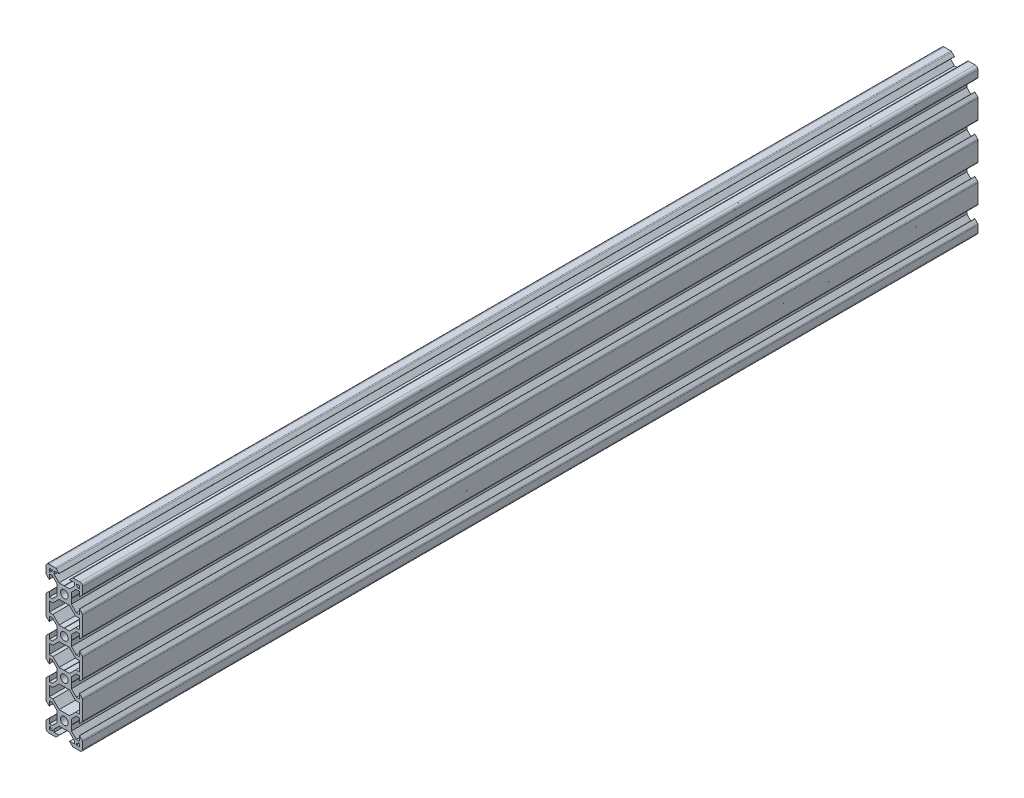
SolidWorks part; units mm, degrees
material "6063-T5"
ref_plane "Front Plane" through (0, 0, 0) normal (0, 0, 1) x (1, 0, 0)
ref_plane "Top Plane" through (0, 0, 0) normal (0, 1, 0) x (1, 0, 0)
ref_plane "Right Plane" through (0, 0, 0) normal (1, 0, 0) x (0, 0, -1)
sketch "Sketch2" plane through (0, 0, 0) normal (0, 0, 1) x (1, 0, 0)
  line L0 (-8.2, 2.8875) -> (-8.2, 5.4975)
  line L3 (-4.9072, 9.9975) -> (-8.5, 9.9975)
  line L4 (-10, 4.9047) -> (-10, 8.4975)
  line L5 (-2.1, 0) -> (-3.8, 0) construction
  line L6 (0, 3.8) -> (0, 2.1) construction
  line L7 (-0.1, 3.9) -> (-2.8404, 3.9)
  line L8 (-3.9, 0.1) -> (-3.9, 2.8383)
  line L9 (-2.89, 8.1975) -> (-5.5, 8.1975)
  line L10 (-6.57, 8.1975) -> (-6.57, 7.6575)
  line L11 (-8.2, 6.5675) -> (-7.66, 6.5675)
  line L12 (-5.5, 8.1975) -> (-5.5, 6.5588)
  line L13 (-6.56, 5.4975) -> (-8.2, 5.4975)
  line L14 (-8.2, 8.1975) -> (-1.4852, 1.4847) construction
  line L15 (-6.56, 5.4975) -> (-3.9, 2.8383)
  line L16 (-5.5, 6.5588) -> (-2.8404, 3.9)
  line L17 (-7.66, 6.5675) -> (-6.57, 7.6575)
  line L18 (-8.7302, 7.6671) -> (-0.5302, -0.5304) construction
  line L19 (-7.6698, 8.7279) -> (0.5302, 0.5304) construction
  line L20 (-8.2, 8.1975) -> (0, 0) construction
  line L21 (-8.2, 6.5675) -> (-8.2, 8.1975)
  line L22 (-8.2, -0.0025) -> (-8.2, 8.1975) construction
  line L23 (-6.57, 8.1975) -> (-8.2, 8.1975)
  line L24 (0, 8.1975) -> (-8.2, 8.1975) construction
  line L25 (-10, -0.0025) -> (-10, 9.9975) construction
  line L26 (0, 9.9975) -> (-10, 9.9975) construction
  line L27 (-2.89, 8.3075) -> (-2.89, 8.1975)
  line L29 (-8.31, 2.8875) -> (-8.2, 2.8875)
  line L30 (-4.3486, 9.7661) -> (-2.89, 8.3075)
  line L31 (-8.31, 2.8875) -> (-9.7686, 4.3461)
  line L34 (-0.1, 3.9) -> (0, 3.8)
  line L35 (-3.9, 0.1) -> (-3.8, 0)
  line L36 (-10, -20) -> (0, -20) construction
  line L37 (0, 0) -> (0, -20) construction
  line L38 (0, -3.9) -> (-2.8404, -3.9)
  line L39 (-3.8, 0) -> (-3.9, -0.1)
  line L40 (-3.9, -0.1) -> (-3.9, -2.84)
  line L41 (-2.8404, -3.9) -> (-6.25, -7.3096)
  line L42 (-3.9, -2.84) -> (-6.56, -5.5)
  line L43 (-8.21, -2.89) -> (-8.21, -5.5)
  line L44 (-6.56, 5.4975) -> (-6.56, -5.5) construction
  line L45 (-6.56, -5.5) -> (-8.21, -5.5)
  line L46 (-6.25, -7.3096) -> (-6.25, -12.7) construction
  line L47 (-6.25, -7.3096) -> (-8.21, -7.3096)
  line L48 (-8.21, -2.89) -> (-8.31, -2.89)
  line L49 (-8.31, -2.89) -> (-9.7657, -4.3457)
  line L51 (-8.21, -7.3096) -> (-8.21, -12.7)
  line L52 (-0.1, -16.1) -> (-2.85, -16.1)
  line L53 (-3.9, -17.16) -> (-3.9, -19.9)
  line L54 (-6.25, -12.7) -> (-2.85, -16.1)
  line L58 (-3.9, -17.16) -> (-6.56, -14.5)
  line L60 (-8.21, -17.11) -> (-8.31, -17.11)
  line L61 (-10, -4.9114) -> (-10, -15.0886)
  line L62 (-9.7657, -15.6543) -> (-8.31, -17.11)
  line L63 (-0.1, -16.1) -> (0, -16.2)
  line L64 (-3.9, -19.9) -> (-3.8, -20)
  line L65 (-8.21, -14.5) -> (-6.56, -14.5)
  line L66 (-8.21, -12.7) -> (-6.25, -12.7)
  line L67 (-10, -30.01) -> (0, -30.01) construction
  line L68 (-8.21, -14.5) -> (-8.21, -17.11)
  line L69 (-3.9, -20.1) -> (-3.8, -20)
  line L71 (-10, -20) -> (0, -20) construction
  line L72 (-8.21, -30.01) -> (-8.21, -27.31)
  line L73 (-10, -30.01) -> (-10, -24.9101)
  line L74 (-8.21, -25.4987) -> (-8.21, -22.8887)
  line L76 (-8.21, -27.31) -> (-6.25, -27.31)
  line L77 (-8.21, -25.4987) -> (-6.56, -25.4987)
  line L85 (-0.1, -23.9) -> (0, -23.8)
  line L95 (-9.7657, -24.3444) -> (-8.31, -22.8887)
  line L96 (-8.21, -22.8887) -> (-8.31, -22.8887)
  line L97 (-3.9, -22.8387) -> (-6.56, -25.4987)
  line L98 (-6.25, -27.31) -> (-2.84, -23.9)
  line L99 (-3.9, -22.8387) -> (-3.9, -20.1)
  line L100 (-0.1, -23.9) -> (-2.84, -23.9)
  arc A1 (-10, 8.4975) -> (-8.5, 9.9975) centre (-8.5, 8.4975) cw
  arc A2 (-9.7686, 4.3461) -> (-10, 4.9047) centre (-9.21, 4.9047) cw
  arc A3 (-4.3486, 9.7661) -> (-4.9072, 9.9975) centre (-4.9072, 9.2075) ccw
  arc A5 (0, 2.1) -> (0, -2.1) centre (0, 0) ccw
  arc A6 (-9.7657, -15.6543) -> (-10, -15.0886) centre (-9.2, -15.0886) cw
  arc A7 (-9.7657, -4.3457) -> (-10, -4.9114) centre (-9.2, -4.9114) ccw
  arc A8 (0, -17.9) -> (0, -22.1) centre (0, -20) ccw
  arc A10 (-9.7657, -24.3444) -> (-10, -24.9101) centre (-9.2, -24.9101) ccw
  point P29 (-10, 9.9975)
  point P39 (-10, 4.5775)
  point P42 (-4.58, 9.9975)
  point P76 (-10, -15.42)
  point P79 (-10, -4.58)
  dimension "D15" = 1.5
  dimension "D22" = 0.79
  dimension "D30" = 2.1
  dimension "D31" = 2.1
  dimension "D51" = 0.8
  dimension "D52" = 2.61
  dimension "D64" = 1.65
  dimension "D53" = 0.8
  dimension "D55" = 3.9
  dimension "D4" = 1.8
  dimension "D5" = 3.43
  dimension "D6" = 3.43
  dimension "D7" = 0.54
  dimension "D8" = 0.54
  dimension "D9" = 1.07
  dimension "D10" = 1.07
  dimension "D11" = 3.9
  dimension "D12" = 3.9
  dimension "D16" = 7.11
  dimension "D17" = 0.11
  dimension "D18" = 1.69
  dimension "D19" = 0.11
  dimension "D20" = 7.11
  dimension "D21" = 1.69
  dimension "D23" = 10
  dimension "D24" = 0.1
  dimension "D25" = 45
  dimension "D26" = 0.1
  dimension "D27" = 45
  dimension "D28" = 1.64
  dimension "D29" = 20
  dimension "D32" = 3.9
  dimension "D33" = 45
  dimension "D34" = 2.74
  dimension "D35" = 45
  dimension "D36" = 1.96
  dimension "D37" = 2.61
  dimension "D38" = 90
  dimension "D39" = 2.61
  dimension "D40" = 3.9
  dimension "D41" = 3.9
  dimension "D42" = 135
  dimension "D44" = 45
  dimension "D45" = 1.8
  dimension "D46" = 0.1
  dimension "D47" = 0.1
  dimension "D48" = 45
  dimension "D49" = 0.1
  dimension "D50" = 45
  dimension "D43" = 5.5
  dimension "D54" = 3.9
  dimension "D56" = 45
  dimension "D57" = 2.7
  dimension "D59" = 45
  dimension "D60" = 0.1
  dimension "D61" = 0.1
  dimension "D62" = 45
  dimension "D63" = 2.84
  dimension "D65" = 1.96
  dimension "D66" = 45
  dimension "D67" = 1.5
  dimension "D13" = 0.75
  dimension "D14" = 0.75
sketch "Sketch3" plane through (0, 0, 0) normal (0, 0, 1) x (1, 0, 0)
  line L0 (-0.1, 3.9) -> (0, 3.8) construction
  line L1 (-0.1, 3.9) -> (-2.8404, 3.9) construction
  line L2 (-5.5, 6.5588) -> (-2.8404, 3.9) construction
  line L3 (-5.5, 8.1975) -> (-5.5, 6.5588) construction
  line L4 (-2.89, 8.1975) -> (-5.5, 8.1975) construction
  line L5 (-7.66, 6.5675) -> (-6.57, 7.6575)
  line L6 (-6.57, 7.6575) -> (-6.57, 8.1975)
  line L7 (-6.57, 8.1975) -> (-8.2, 8.1975)
  line L8 (-8.2, 8.1975) -> (-8.2, 6.5675)
  line L9 (-8.2, 6.5675) -> (-7.66, 6.5675)
  line L10 (-7.66, 6.5675) -> (-6.57, 7.6575)
  line L11 (-6.57, 7.6575) -> (-6.57, 8.1975)
  line L12 (-6.57, 8.1975) -> (-8.2, 8.1975)
  line L13 (-8.2, 8.1975) -> (-8.2, 6.5675)
  line L14 (-8.2, 6.5675) -> (-7.66, 6.5675)
  line L15 (-2.89, 8.3075) -> (-2.89, 8.1975) construction
  line L16 (-4.3486, 9.7661) -> (-2.89, 8.3075) construction
  line L17 (-4.9072, 9.9975) -> (-8.5, 9.9975) construction
  line L18 (-10, 4.9047) -> (-10, 8.4975) construction
  line L19 (-8.31, 2.8875) -> (-9.7686, 4.3461) construction
  line L20 (-8.31, 2.8875) -> (-8.2, 2.8875) construction
  line L21 (-8.2, 2.8875) -> (-8.2, 5.4975) construction
  line L22 (-6.56, 5.4975) -> (-8.2, 5.4975) construction
  line L23 (-6.56, 5.4975) -> (-3.9, 2.8383) construction
  line L24 (-3.9, 0.1) -> (-3.9, 2.8383) construction
  line L25 (-3.9, 0.1) -> (-3.8, 0) construction
  line L26 (-3.8, 0) -> (-3.9, -0.1) construction
  line L27 (-3.9, -0.1) -> (-3.9, -2.84) construction
  line L28 (-3.9, -2.84) -> (-6.56, -5.5) construction
  line L29 (-6.56, -5.5) -> (-8.21, -5.5) construction
  line L30 (-8.21, -2.89) -> (-8.21, -5.5) construction
  line L31 (-8.21, -2.89) -> (-8.31, -2.89) construction
  line L32 (-8.31, -2.89) -> (-9.7657, -4.3457) construction
  line L33 (-10, -4.9114) -> (-10, -15.0886) construction
  line L34 (-9.7657, -15.6543) -> (-8.31, -17.11) construction
  line L35 (-8.21, -17.11) -> (-8.31, -17.11) construction
  line L36 (-8.21, -14.5) -> (-8.21, -17.11) construction
  line L37 (-8.21, -14.5) -> (-6.56, -14.5) construction
  line L38 (-3.9, -17.16) -> (-6.56, -14.5) construction
  line L39 (-3.9, -17.16) -> (-3.9, -19.9) construction
  line L40 (-3.9, -19.9) -> (-3.8, -20) construction
  line L41 (-3.9, -20.1) -> (-3.8, -20) construction
  line L42 (-3.9, -22.8387) -> (-3.9, -20.1) construction
  line L43 (-3.9, -22.8387) -> (-6.56, -25.4987) construction
  line L44 (-8.21, -25.4987) -> (-6.56, -25.4987) construction
  line L45 (-8.21, -25.4987) -> (-8.21, -22.8887) construction
  line L46 (-8.21, -22.8887) -> (-8.31, -22.8887) construction
  line L47 (-9.7657, -24.3444) -> (-8.31, -22.8887) construction
  line L48 (-10, -30.01) -> (-10, -24.9101) construction
  line L49 (0, -3.9) -> (-2.8404, -3.9) construction
  line L50 (-2.8404, -3.9) -> (-6.25, -7.3096) construction
  line L51 (-6.25, -7.3096) -> (-8.21, -7.3096) construction
  line L52 (-8.21, -7.3096) -> (-8.21, -12.7) construction
  line L53 (-8.21, -12.7) -> (-6.25, -12.7) construction
  line L54 (-6.25, -12.7) -> (-2.85, -16.1) construction
  line L55 (-0.1, -16.1) -> (-2.85, -16.1) construction
  line L56 (-0.1, -16.1) -> (0, -16.2) construction
  line L57 (-0.1, -23.9) -> (0, -23.8) construction
  line L58 (-0.1, -23.9) -> (-2.84, -23.9) construction
  line L59 (-6.25, -27.31) -> (-2.84, -23.9) construction
  line L60 (-8.21, -27.31) -> (-6.25, -27.31) construction
  line L61 (-8.21, -30.01) -> (-8.21, -27.31) construction
  line L62 (-0.1, 3.9) -> (0, 3.8)
  line L63 (-0.1, 3.9) -> (-2.8404, 3.9)
  line L64 (-5.5, 6.5588) -> (-2.8404, 3.9)
  line L65 (-5.5, 8.1975) -> (-5.5, 6.5588)
  line L66 (-2.89, 8.1975) -> (-5.5, 8.1975)
  line L67 (-2.89, 8.3075) -> (-2.89, 8.1975)
  line L68 (-4.3486, 9.7661) -> (-2.89, 8.3075)
  line L69 (-4.9072, 9.9975) -> (-8.5, 9.9975)
  line L70 (-10, 4.9047) -> (-10, 8.4975)
  line L71 (-8.31, 2.8875) -> (-9.7686, 4.3461)
  line L72 (-8.31, 2.8875) -> (-8.2, 2.8875)
  line L73 (-8.2, 2.8875) -> (-8.2, 5.4975)
  line L74 (-6.56, 5.4975) -> (-8.2, 5.4975)
  line L75 (-6.56, 5.4975) -> (-3.9, 2.8383)
  line L76 (-3.9, 0.1) -> (-3.9, 2.8383)
  line L77 (-3.9, 0.1) -> (-3.8, 0)
  line L78 (-3.8, 0) -> (-3.9, -0.1)
  line L79 (-3.9, -0.1) -> (-3.9, -2.84)
  line L80 (-3.9, -2.84) -> (-6.56, -5.5)
  line L81 (-6.56, -5.5) -> (-8.21, -5.5)
  line L82 (-8.21, -2.89) -> (-8.21, -5.5)
  line L83 (-8.21, -2.89) -> (-8.31, -2.89)
  line L84 (-8.31, -2.89) -> (-9.7657, -4.3457)
  line L85 (-10, -4.9114) -> (-10, -15.0886)
  line L86 (-9.7657, -15.6543) -> (-8.31, -17.11)
  line L87 (-8.21, -17.11) -> (-8.31, -17.11)
  line L88 (-8.21, -14.5) -> (-8.21, -17.11)
  line L89 (-8.21, -14.5) -> (-6.56, -14.5)
  line L90 (-3.9, -17.16) -> (-6.56, -14.5)
  line L91 (-3.9, -17.16) -> (-3.9, -19.9)
  line L92 (-3.9, -19.9) -> (-3.8, -20)
  line L93 (-3.9, -20.1) -> (-3.8, -20)
  line L94 (-3.9, -22.8387) -> (-3.9, -20.1)
  line L95 (-3.9, -22.8387) -> (-6.56, -25.4987)
  line L96 (-8.21, -25.4987) -> (-6.56, -25.4987)
  line L97 (-8.21, -25.4987) -> (-8.21, -22.8887)
  line L98 (-8.21, -22.8887) -> (-8.31, -22.8887)
  line L99 (-9.7657, -24.3444) -> (-8.31, -22.8887)
  line L100 (-10, -35.1099) -> (-10, -24.9101)
  line L101 (2.8404, -3.9) -> (-2.8404, -3.9)
  line L102 (-2.8404, -3.9) -> (-6.25, -7.3096)
  line L103 (-6.25, -7.3096) -> (-8.21, -7.3096)
  line L104 (-8.21, -7.3096) -> (-8.21, -12.7)
  line L105 (-8.21, -12.7) -> (-6.25, -12.7)
  line L106 (-6.25, -12.7) -> (-2.85, -16.1)
  line L107 (-0.1, -16.1) -> (-2.85, -16.1)
  line L108 (-0.1, -16.1) -> (0, -16.2)
  line L109 (-0.1, -23.9) -> (0, -23.8)
  line L110 (-0.1, -23.9) -> (-2.84, -23.9)
  line L111 (-6.25, -27.31) -> (-2.84, -23.9)
  line L112 (-8.21, -27.31) -> (-6.25, -27.31)
  line L113 (-8.21, -32.71) -> (-8.21, -27.31)
  line L114 (0, 0) -> (0, -20) construction
  line L115 (-10, -30.01) -> (0, -30.01) construction
  line L116 (0, 0) -> (0, -20) construction
  line L117 (-10, -30.01) -> (10, -30.01) construction
  line L118 (8.21, -32.71) -> (8.21, -27.31)
  line L119 (8.21, -27.31) -> (6.25, -27.31)
  line L120 (6.25, -27.31) -> (2.84, -23.9)
  line L121 (0.1, -23.9) -> (2.84, -23.9)
  line L122 (0.1, -23.9) -> (0, -23.8)
  line L123 (0.1, -16.1) -> (0, -16.2)
  line L124 (0.1, -16.1) -> (2.85, -16.1)
  line L125 (6.25, -12.7) -> (2.85, -16.1)
  line L126 (8.21, -12.7) -> (6.25, -12.7)
  line L127 (8.21, -7.3096) -> (8.21, -12.7)
  line L128 (6.25, -7.3096) -> (8.21, -7.3096)
  line L129 (2.8404, -3.9) -> (6.25, -7.3096)
  line L130 (10, -35.1099) -> (10, -24.9101)
  line L131 (9.7657, -24.3444) -> (8.31, -22.8887)
  line L132 (8.21, -22.8887) -> (8.31, -22.8887)
  line L133 (8.21, -25.4987) -> (8.21, -22.8887)
  line L134 (8.21, -25.4987) -> (6.56, -25.4987)
  line L135 (3.9, -22.8387) -> (6.56, -25.4987)
  line L136 (3.9, -22.8387) -> (3.9, -20.1)
  line L137 (3.9, -20.1) -> (3.8, -20)
  line L138 (3.9, -19.9) -> (3.8, -20)
  line L139 (3.9, -17.16) -> (3.9, -19.9)
  line L140 (3.9, -17.16) -> (6.56, -14.5)
  line L141 (8.21, -14.5) -> (6.56, -14.5)
  line L142 (8.21, -14.5) -> (8.21, -17.11)
  line L143 (8.21, -17.11) -> (8.31, -17.11)
  line L144 (9.7657, -15.6543) -> (8.31, -17.11)
  line L145 (10, -4.9114) -> (10, -15.0886)
  line L146 (8.31, -2.89) -> (9.7657, -4.3457)
  line L147 (8.21, -2.89) -> (8.31, -2.89)
  line L148 (8.21, -2.89) -> (8.21, -5.5)
  line L149 (6.56, -5.5) -> (8.21, -5.5)
  line L150 (3.9, -2.84) -> (6.56, -5.5)
  line L151 (3.9, -0.1) -> (3.9, -2.84)
  line L152 (3.8, 0) -> (3.9, -0.1)
  line L153 (3.9, 0.1) -> (3.8, 0)
  line L154 (3.9, 0.1) -> (3.9, 2.8383)
  line L155 (6.56, 5.4975) -> (3.9, 2.8383)
  line L156 (6.56, 5.4975) -> (8.2, 5.4975)
  line L157 (8.2, 2.8875) -> (8.2, 5.4975)
  line L158 (8.31, 2.8875) -> (8.2, 2.8875)
  line L159 (8.31, 2.8875) -> (9.7686, 4.3461)
  line L160 (10, 4.9047) -> (10, 8.4975)
  line L161 (4.9072, 9.9975) -> (8.5, 9.9975)
  line L162 (4.3486, 9.7661) -> (2.89, 8.3075)
  line L163 (2.89, 8.3075) -> (2.89, 8.1975)
  line L164 (2.89, 8.1975) -> (5.5, 8.1975)
  line L165 (5.5, 8.1975) -> (5.5, 6.5588)
  line L166 (5.5, 6.5588) -> (2.8404, 3.9)
  line L167 (0.1, 3.9) -> (2.8404, 3.9)
  line L168 (0.1, 3.9) -> (0, 3.8)
  line L169 (8.2, 6.5675) -> (7.66, 6.5675)
  line L170 (8.2, 8.1975) -> (8.2, 6.5675)
  line L171 (6.57, 8.1975) -> (8.2, 8.1975)
  line L172 (6.57, 7.6575) -> (6.57, 8.1975)
  line L173 (7.66, 6.5675) -> (6.57, 7.6575)
  line L174 (0, -60.02) -> (0, -40.02) construction
  line L175 (7.66, -66.5875) -> (6.57, -67.6775)
  line L176 (6.57, -67.6775) -> (6.57, -68.2175)
  line L177 (6.57, -68.2175) -> (8.2, -68.2175)
  line L178 (8.2, -68.2175) -> (8.2, -66.5875)
  line L179 (8.2, -66.5875) -> (7.66, -66.5875)
  line L180 (0.1, -63.92) -> (0, -63.82)
  line L181 (0.1, -63.92) -> (2.8404, -63.92)
  line L182 (5.5, -66.5788) -> (2.8404, -63.92)
  line L183 (5.5, -68.2175) -> (5.5, -66.5788)
  line L184 (2.89, -68.2175) -> (5.5, -68.2175)
  line L185 (2.89, -68.3275) -> (2.89, -68.2175)
  line L186 (4.3486, -69.7861) -> (2.89, -68.3275)
  line L187 (4.9072, -70.0175) -> (8.5, -70.0175)
  line L188 (10, -64.9247) -> (10, -68.5175)
  line L189 (8.31, -62.9075) -> (9.7686, -64.3661)
  line L190 (8.31, -62.9075) -> (8.2, -62.9075)
  line L191 (8.2, -62.9075) -> (8.2, -65.5175)
  line L192 (6.56, -65.5175) -> (8.2, -65.5175)
  line L193 (6.56, -65.5175) -> (3.9, -62.8583)
  line L194 (3.9, -60.12) -> (3.9, -62.8583)
  line L195 (3.9, -60.12) -> (3.8, -60.02)
  line L196 (3.8, -60.02) -> (3.9, -59.92)
  line L197 (3.9, -59.92) -> (3.9, -57.18)
  line L198 (3.9, -57.18) -> (6.56, -54.52)
  line L199 (6.56, -54.52) -> (8.21, -54.52)
  line L200 (8.21, -57.13) -> (8.21, -54.52)
  line L201 (8.21, -57.13) -> (8.31, -57.13)
  line L202 (8.31, -57.13) -> (9.7657, -55.6743)
  line L203 (10, -55.1086) -> (10, -44.9314)
  line L204 (9.7657, -44.3657) -> (8.31, -42.91)
  line L205 (8.21, -42.91) -> (8.31, -42.91)
  line L206 (8.21, -45.52) -> (8.21, -42.91)
  line L207 (8.21, -45.52) -> (6.56, -45.52)
  line L208 (3.9, -42.86) -> (6.56, -45.52)
  line L209 (3.9, -42.86) -> (3.9, -40.12)
  line L210 (3.9, -40.12) -> (3.8, -40.02)
  line L211 (3.9, -39.92) -> (3.8, -40.02)
  line L212 (3.9, -37.1813) -> (3.9, -39.92)
  line L213 (3.9, -37.1813) -> (6.56, -34.5213)
  line L214 (8.21, -34.5213) -> (6.56, -34.5213)
  line L215 (8.21, -34.5213) -> (8.21, -37.1313)
  line L216 (8.21, -37.1313) -> (8.31, -37.1313)
  line L217 (9.7657, -35.6756) -> (8.31, -37.1313)
  line L218 (2.8404, -56.12) -> (6.25, -52.7104)
  line L219 (6.25, -52.7104) -> (8.21, -52.7104)
  line L220 (8.21, -52.7104) -> (8.21, -47.32)
  line L221 (8.21, -47.32) -> (6.25, -47.32)
  line L222 (6.25, -47.32) -> (2.85, -43.92)
  line L223 (0.1, -43.92) -> (2.85, -43.92)
  line L224 (0.1, -43.92) -> (0, -43.82)
  line L225 (0.1, -36.12) -> (0, -36.22)
  line L226 (0.1, -36.12) -> (2.84, -36.12)
  line L227 (6.25, -32.71) -> (2.84, -36.12)
  line L228 (8.21, -32.71) -> (6.25, -32.71)
  line L229 (-8.21, -32.71) -> (-6.25, -32.71)
  line L230 (-6.25, -32.71) -> (-2.84, -36.12)
  line L231 (-0.1, -36.12) -> (-2.84, -36.12)
  line L232 (-0.1, -36.12) -> (0, -36.22)
  line L233 (-0.1, -43.92) -> (0, -43.82)
  line L234 (-0.1, -43.92) -> (-2.85, -43.92)
  line L235 (-6.25, -47.32) -> (-2.85, -43.92)
  line L236 (-8.21, -47.32) -> (-6.25, -47.32)
  line L237 (-8.21, -52.7104) -> (-8.21, -47.32)
  line L238 (-6.25, -52.7104) -> (-8.21, -52.7104)
  line L239 (-2.8404, -56.12) -> (-6.25, -52.7104)
  line L240 (2.8404, -56.12) -> (-2.8404, -56.12)
  line L241 (-9.7657, -35.6756) -> (-8.31, -37.1313)
  line L242 (-8.21, -37.1313) -> (-8.31, -37.1313)
  line L243 (-8.21, -34.5213) -> (-8.21, -37.1313)
  line L244 (-8.21, -34.5213) -> (-6.56, -34.5213)
  line L245 (-3.9, -37.1813) -> (-6.56, -34.5213)
  line L246 (-3.9, -37.1813) -> (-3.9, -39.92)
  line L247 (-3.9, -39.92) -> (-3.8, -40.02)
  line L248 (-3.9, -40.12) -> (-3.8, -40.02)
  line L249 (-3.9, -42.86) -> (-3.9, -40.12)
  line L250 (-3.9, -42.86) -> (-6.56, -45.52)
  line L251 (-8.21, -45.52) -> (-6.56, -45.52)
  line L252 (-8.21, -45.52) -> (-8.21, -42.91)
  line L253 (-8.21, -42.91) -> (-8.31, -42.91)
  line L254 (-9.7657, -44.3657) -> (-8.31, -42.91)
  line L255 (-10, -55.1086) -> (-10, -44.9314)
  line L256 (-8.31, -57.13) -> (-9.7657, -55.6743)
  line L257 (-8.21, -57.13) -> (-8.31, -57.13)
  line L258 (-8.21, -57.13) -> (-8.21, -54.52)
  line L259 (-6.56, -54.52) -> (-8.21, -54.52)
  line L260 (-3.9, -57.18) -> (-6.56, -54.52)
  line L261 (-3.9, -59.92) -> (-3.9, -57.18)
  line L262 (-3.8, -60.02) -> (-3.9, -59.92)
  line L263 (-3.9, -60.12) -> (-3.8, -60.02)
  line L264 (-3.9, -60.12) -> (-3.9, -62.8583)
  line L265 (-6.56, -65.5175) -> (-3.9, -62.8583)
  line L266 (-6.56, -65.5175) -> (-8.2, -65.5175)
  line L267 (-8.2, -62.9075) -> (-8.2, -65.5175)
  line L268 (-8.31, -62.9075) -> (-8.2, -62.9075)
  line L269 (-8.31, -62.9075) -> (-9.7686, -64.3661)
  line L270 (-10, -64.9247) -> (-10, -68.5175)
  line L271 (-4.9072, -70.0175) -> (-8.5, -70.0175)
  line L272 (-4.3486, -69.7861) -> (-2.89, -68.3275)
  line L273 (-2.89, -68.3275) -> (-2.89, -68.2175)
  line L274 (-2.89, -68.2175) -> (-5.5, -68.2175)
  line L275 (-5.5, -68.2175) -> (-5.5, -66.5788)
  line L276 (-5.5, -66.5788) -> (-2.8404, -63.92)
  line L277 (-0.1, -63.92) -> (-2.8404, -63.92)
  line L278 (-0.1, -63.92) -> (0, -63.82)
  line L279 (-8.2, -66.5875) -> (-7.66, -66.5875)
  line L280 (-8.2, -68.2175) -> (-8.2, -66.5875)
  line L281 (-6.57, -68.2175) -> (-8.2, -68.2175)
  line L282 (-6.57, -67.6775) -> (-6.57, -68.2175)
  line L283 (-7.66, -66.5875) -> (-6.57, -67.6775)
  arc A0 (0, 2.1) -> (0, -2.1) centre (0, 0) ccw construction
  arc A1 (0, -17.9) -> (0, -22.1) centre (0, -20) ccw construction
  arc A2 (-4.3486, 9.7661) -> (-4.9072, 9.9975) centre (-4.9072, 9.2075) ccw construction
  arc A3 (-8.5, 9.9975) -> (-10, 8.4975) centre (-8.5, 8.4975) ccw construction
  arc A4 (-10, 4.9047) -> (-9.7686, 4.3461) centre (-9.21, 4.9047) ccw construction
  arc A5 (-9.7657, -4.3457) -> (-10, -4.9114) centre (-9.2, -4.9114) ccw construction
  arc A6 (-10, -15.0886) -> (-9.7657, -15.6543) centre (-9.2, -15.0886) ccw construction
  arc A7 (-9.7657, -24.3444) -> (-10, -24.9101) centre (-9.2, -24.9101) ccw construction
  circle A8 centre (0, 0) radius 2.1
  circle A9 centre (0, -20) radius 2.1
  arc A10 (-4.3486, 9.7661) -> (-4.9072, 9.9975) centre (-4.9072, 9.2075) ccw
  arc A11 (-8.5, 9.9975) -> (-10, 8.4975) centre (-8.5, 8.4975) ccw
  arc A12 (-10, 4.9047) -> (-9.7686, 4.3461) centre (-9.21, 4.9047) ccw
  arc A13 (-9.7657, -4.3457) -> (-10, -4.9114) centre (-9.2, -4.9114) ccw
  arc A14 (-10, -15.0886) -> (-9.7657, -15.6543) centre (-9.2, -15.0886) ccw
  arc A15 (-9.7657, -24.3444) -> (-10, -24.9101) centre (-9.2, -24.9101) ccw
  arc A16 (9.7657, -24.3444) -> (10, -24.9101) centre (9.2, -24.9101) cw
  arc A17 (10, -15.0886) -> (9.7657, -15.6543) centre (9.2, -15.0886) cw
  arc A18 (9.7657, -4.3457) -> (10, -4.9114) centre (9.2, -4.9114) cw
  arc A19 (10, 4.9047) -> (9.7686, 4.3461) centre (9.21, 4.9047) cw
  arc A20 (8.5, 9.9975) -> (10, 8.4975) centre (8.5, 8.4975) cw
  arc A21 (4.3486, 9.7661) -> (4.9072, 9.9975) centre (4.9072, 9.2075) cw
  arc A22 (4.3486, -69.7861) -> (4.9072, -70.0175) centre (4.9072, -69.2275) ccw
  arc A23 (8.5, -70.0175) -> (10, -68.5175) centre (8.5, -68.5175) ccw
  arc A24 (10, -64.9247) -> (9.7686, -64.3661) centre (9.21, -64.9247) ccw
  arc A25 (9.7657, -55.6743) -> (10, -55.1086) centre (9.2, -55.1086) ccw
  arc A26 (10, -44.9314) -> (9.7657, -44.3657) centre (9.2, -44.9314) ccw
  arc A27 (9.7657, -35.6756) -> (10, -35.1099) centre (9.2, -35.1099) ccw
  arc A28 (-9.7657, -35.6756) -> (-10, -35.1099) centre (-9.2, -35.1099) cw
  arc A29 (-10, -44.9314) -> (-9.7657, -44.3657) centre (-9.2, -44.9314) cw
  arc A30 (-9.7657, -55.6743) -> (-10, -55.1086) centre (-9.2, -55.1086) cw
  arc A31 (-10, -64.9247) -> (-9.7686, -64.3661) centre (-9.21, -64.9247) cw
  arc A32 (-8.5, -70.0175) -> (-10, -68.5175) centre (-8.5, -68.5175) cw
  arc A33 (-4.3486, -69.7861) -> (-4.9072, -70.0175) centre (-4.9072, -69.2275) cw
  circle A34 centre (0, -40.02) radius 2.1
  circle A35 centre (0, -60.02) radius 2.1
  point P240 (8.21, -30.01)
  point P288 (-0.1, 9.9975)
  point P289 (0, -70.0175)
  point P290 (-10, -60.02)
  point P291 (10, -60.02)
  point P292 (10, -40.02)
  point P293 (-10, -40.02)
  point P294 (-10, -20)
  point P295 (10, -20)
  point P296 (10, 0)
  point P297 (-10, 0)
  point P298 (-45.6583, 8.4975)
  dimension "D1" = 0
extrude "Boss-Extrude1" add sketch "Sketch3" against normal mid plane 489.5
